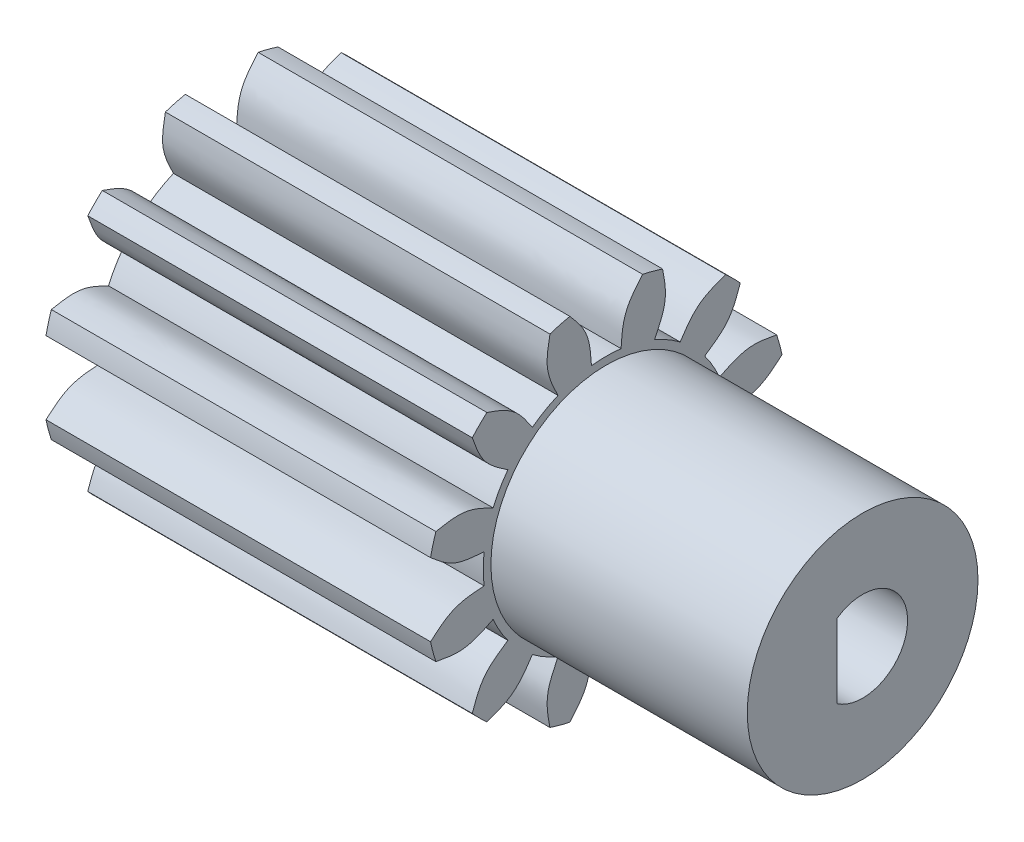
SolidWorks part; units mm, degrees
ref_plane "Front" through (0, 0, 0) normal (0, 0, 1) x (1, 0, 0)
ref_plane "Top" through (0, 0, 0) normal (0, 1, 0) x (1, 0, 0)
ref_plane "Right" through (0, 0, 0) normal (1, 0, 0) x (0, 0, -1)
sketch "Ritning 1" plane through (0, 0, 0) normal (0, 0, 1) x (1, 0, 0)
  line L0 (12.5, 1) -> (2.5, 1)
  line L1 (2.5, 1) -> (2.5, 3.5)
  line L2 (2.5, 3.5) -> (-12.5, 3.5)
  line L3 (12.5, 1) -> (12.5, -3.5)
  line L4 (-12.5, 3.5) -> (-12.5, -3.5)
  line L5 (-12.5, -3.5) -> (12.5, -3.5)
  dimension "D1" = 2.5
  dimension "D2" = 12.5
  dimension "D3" = 12.5
  dimension "D4" = 1
  dimension "D5" = 3.5
  dimension "D6" = 3.5
revolve "Kugghjulsämne" add sketch "Ritning 1" angle 360 about L5
sketch "Ritning 2" plane through (-12.5, 0, 0) normal (-1, 0, 0) x (0, 0, 1)
  line L0 (0, -3.5) -> (0, 3.5) construction
  line L1 (1.4199, 3.3545) -> (0, 4.7744)
  line L2 (-1.4199, 3.3545) -> (0, 4.7744)
  line L3 (0, -3.5) -> (1.4199, -3.5) construction
  arc A0 (0.5768, 1.2652) -> (-0.5768, 1.2652) centre (0, -3.5) ccw
  circle A1 centre (0, -3.5) radius 7 construction
  spline S0 degree 3 poles (1.4199, 3.3545) (1.173, 3.0671) (0.6581, 2.4675) (0.6046, 1.6769) (0.5768, 1.2652) knots 0 0 0 0 0.479362 1 1 1 1
  spline S1 degree 3 poles (-1.4199, 3.3545) (-1.173, 3.0671) (-0.6581, 2.4675) (-0.6046, 1.6769) (-0.5768, 1.2652) knots 0 0 0 0 0.479362 1 1 1 1
  dimension "D1" = 4.8
  dimension "D2" = 0.5768
  dimension "D3" = 0.7854
  dimension "D4" = 1.4199
  dimension "D5" = 5.9484
  dimension "D6" = 0.7854
  dimension "D7" = 6.8545
extrude "Kugglucka" cut sketch "Ritning 2" against normal up to surface (15 mm away) up to face at (2.5, -3.5, 7)
pattern_circular "CirPattern" count 12 over 360 about axis through (-12.5, -3.5, 0) along (-1, 0, 0) of "Kugglucka"
sketch "Sketch1" plane through (12.5, 0, 0) normal (1, 0, 0) x (0, 0, -1)
  line L0 (0, 1.3) -> (0, -8.3) construction
  line L1 (0, -8.3) -> (4.8, -3.5) construction
  line L2 (4.8, -3.5) -> (0, -3.5) construction
  arc A0 (0.5768, 1.2652) -> (-0.5768, 1.2652) centre (0, -3.5) ccw construction
  arc A1 (-0.5768, -8.2652) -> (0.5768, -8.2652) centre (0, -3.5) ccw construction
  arc A2 (4.7652, -4.0768) -> (4.7652, -2.9232) centre (0, -3.5) ccw construction
  circle A3 centre (0, -3.5) radius 1.754
extrude "Cut-Extrude1" cut sketch "Sketch1" against normal blind 10
sketch "Sketch3" plane through (12.5, 0, 0) normal (1, 0, 0) x (0, 0, -1)
  line L0 (-1, -1.3227) -> (-1, -6.2089)
  line L1 (-1, -6.2089) -> (-3.3306, -3.3671)
  line L2 (-3.3306, -3.3671) -> (-1, -1.3227)
  line L3 (0, -1.746) -> (0, -3.5) construction
  circle A0 centre (0, -3.5) radius 1.754 construction
  dimension "D1" = 1
extrude "Boss-Extrude1" add sketch "Sketch3" against normal blind 10
